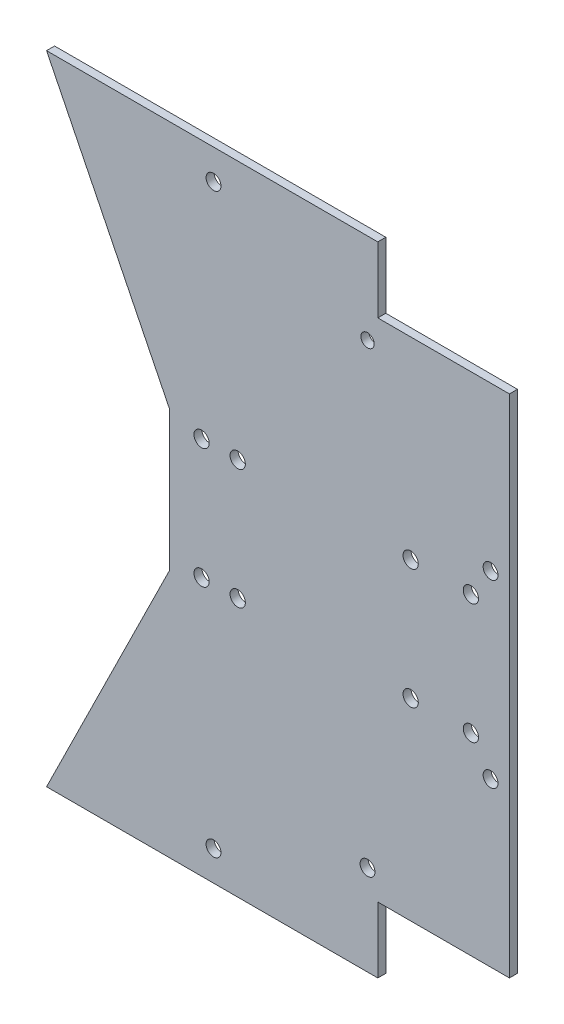
SolidWorks part; units mm, degrees
material "Thornel Mat VMA"
ref_plane "Front Plane" through (0, 0, 0) normal (0, 0, 1) x (1, 0, 0)
ref_plane "Top Plane" through (0, 0, 0) normal (0, 1, 0) x (1, 0, 0)
ref_plane "Right Plane" through (0, 0, 0) normal (1, 0, 0) x (0, 0, -1)
sketch "Sketch2" plane through (0, 0, 0) normal (0, 0, 1) x (-1, 0, 0)
  line L11 (-2.9301, 168.7083) -> (38.7094, 168.7083)
  line L12 (-2.9301, 8.6883) -> (38.7094, 8.6883)
  line L13 (38.7094, -12.1397) -> (38.7094, 8.6883)
  line L14 (143.4971, -12.1397) -> (38.7094, -12.1397)
  line L15 (38.7094, 189.5363) -> (38.7094, 168.7083)
  line L16 (143.4971, 189.5363) -> (38.7094, 189.5363)
  line L17 (104.6174, 110.8598) -> (143.4971, 189.5363)
  line L18 (104.6174, 66.5368) -> (143.4971, -12.1397)
  line L19 (104.6174, 66.5368) -> (72.8674, 66.5368)
  line L20 (72.8674, 66.5368) -> (72.8674, 110.8598)
  line L21 (104.6174, 110.8598) -> (72.8674, 110.8598)
  line L22 (-2.9301, 168.7083) -> (-2.9301, 8.6883)
  line L23 (41.9566, 19.6103) -> (41.9566, 13.2603) construction
  circle A0 centre (41.9566, 160.9613) radius 2.3495
  circle A1 centre (90.6739, 180.0113) radius 2.3495
  circle A2 centre (90.6739, -2.6147) radius 2.3495
  circle A3 centre (3.0351, 117.2098) radius 2.3495
  circle A4 centre (3.0351, 60.1868) radius 2.3495
  circle A5 centre (41.9566, 16.4353) radius 2.0955
  point P36 (41.9566, 16.4353)
  dimension "D3" = 4.699
  dimension "D7" = 31.75
  dimension "D8" = 41.6395
  dimension "D9" = 20.828
  dimension "D10" = 160.02
  dimension "D11" = 20.828
  dimension "D12" = 41.6395
  dimension "D13" = 104.7876
  dimension "D14" = 116.297
  dimension "D15" = 116.297
  dimension "D16" = 44.323
  dimension "D17" = 26.297
  dimension "D18" = 9.525
  dimension "D19" = 28.575
  dimension "D20" = 7.747
  dimension "D21" = 51.9645
  dimension "D22" = 51.4985
  dimension "D23" = 5.9651
  dimension "D24" = 51.4985
  dimension "D25" = 5.9651
  dimension "D26" = 7.747
  dimension "D27" = 3.2471
  dimension "D28" = 9.525
  dimension "D29" = 51.9645
extrude "Boss-Extrude1" add sketch "Sketch2" along normal blind 2.54
sketch "Sketch3" plane through (0, 0, 2.54) normal (0, 0, 1) x (1, 0, 0)
  line L1 (-104.6174, -66.5368) -> (-72.8674, -66.5368)
  line L2 (-104.6174, -66.5368) -> (-104.6174, -110.8598)
  line L3 (-104.6174, -110.8598) -> (-72.8674, -110.8598)
  line L4 (-72.8674, -66.5368) -> (-72.8674, -110.8598)
extrude "Boss-Extrude2" add sketch "Sketch3" against normal up to surface (2.54 mm away) up to face at (-65.9118, -88.6983, 0)
sketch "Sketch4" plane through (0, 0, 2.54) normal (0, 0, 1) x (1, 0, 0)
  line L0 (-104.6174, -66.5368) -> (-104.6174, -72.8868)
  line L1 (-104.6174, -66.5368) -> (-104.6174, -110.8598) construction
  line L2 (-104.6174, -69.7118) -> (2.9301, -69.7118) construction
  line L3 (2.9301, -168.7083) -> (2.9301, -8.6883) construction
  line L4 (-104.6174, -88.6983) -> (2.9301, -88.6983) construction
  line L5 (-104.6174, -107.6848) -> (2.9301, -107.6848) construction
  line L6 (-104.6174, -110.8598) -> (-104.6174, -104.5098)
  circle A0 centre (-94.4574, -69.7118) radius 2.413
  circle A1 centre (-83.0274, -69.7118) radius 2.413
  circle A2 centre (-28.3119, -69.7118) radius 2.413
  circle A3 centre (-9.2619, -69.7118) radius 2.413
  circle A4 centre (-9.2619, -107.6848) radius 2.413
  circle A5 centre (-28.3119, -107.6848) radius 2.413
  circle A6 centre (-83.0274, -107.6848) radius 2.413
  circle A7 centre (-94.4574, -107.6848) radius 2.413
  dimension "D2" = 10.16
  dimension "D4" = 4.826
  dimension "D5" = 4.826
  dimension "D8" = 4.826
  dimension "D9" = 4.826
  dimension "D1" = 3.175
  dimension "D3" = 11.43
  dimension "D6" = 19.05
  dimension "D7" = 12.192
extrude "Cut-Extrude1" cut sketch "Sketch4" against normal through all contours A0 | A1 | A2 | A3 | A4 | A5 | A6 | A7
